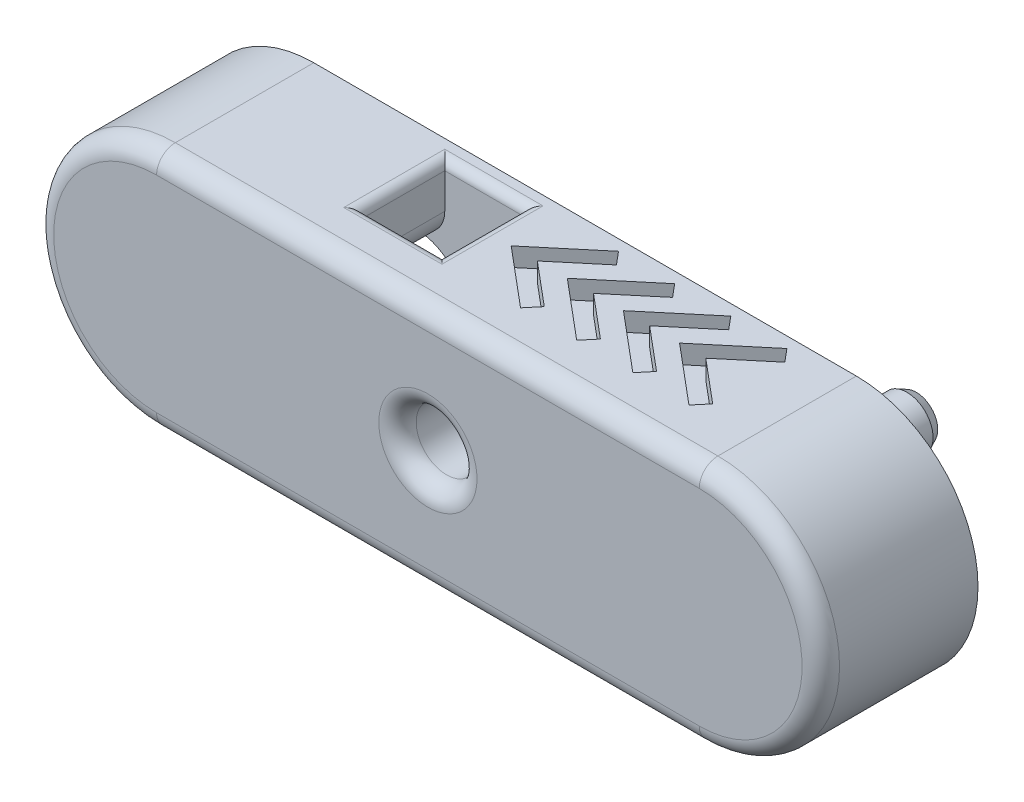
SolidWorks part; units mm, degrees
ref_plane "Front Plane" through (0, 0, 0) normal (0, 0, 1) x (1, 0, 0)
ref_plane "Top Plane" through (0, 0, 0) normal (0, 1, 0) x (1, 0, 0)
ref_plane "Right Plane" through (0, 0, 0) normal (1, 0, 0) x (0, 0, -1)
sketch "Sketch1" plane through (0, 0, 0) normal (0, 0, 1) x (1, 0, 0)
  line L0 (29, 13) -> (-29, 13) construction
  line L1 (-29, -13) -> (29, -13) construction
  line L2 (29, 13) -> (-29, 13)
  line L3 (-29, -13) -> (29, -13)
  arc A0 (-29, 13) -> (-29, -13) centre (-29, 0) ccw construction
  arc A1 (29, -13) -> (29, 13) centre (29, 0) ccw construction
  arc A2 (-29, 13) -> (-29, -13) centre (-29, 0) ccw
  arc A3 (29, -13) -> (29, 13) centre (29, 0) ccw
  circle A9 centre (-35, 0) radius 3 construction
  circle A10 centre (17, 6) radius 3 construction
  circle A11 centre (17, -6) radius 3 construction
  circle A12 centre (29, -6) radius 3 construction
  circle A13 centre (29, 6) radius 3 construction
  circle A14 centre (-35, 0) radius 3
  circle A15 centre (17, 6) radius 3
  circle A16 centre (17, -6) radius 3
  circle A17 centre (29, -6) radius 3
  circle A18 centre (29, 6) radius 3
  circle A19 centre (17, 6) radius 2.8
  circle A20 centre (29, 6) radius 2.8
  circle A21 centre (29, -6) radius 2.8
  circle A22 centre (17, -6) radius 2.8
  circle A23 centre (-35, 0) radius 2.8
  circle A24 centre (-16, 0) radius 5.05 construction
  circle A25 centre (0, 0) radius 5.05 construction
  circle A26 centre (-16, 0) radius 5.05
  circle A27 centre (0, 0) radius 5.05
  dimension "D1" = 0.2
extrude "Boss-Extrude1" add sketch "Sketch1" against normal offset from surface (6.4 mm away) 1 contours A23 | A20 | A21 region at (29, 6, 0) region at (29, -6, 0) region at (-35, 0, 0)
extrude "Boss-Extrude2" add sketch "Sketch1<3>" along normal blind 2 contours L3 A3 L2 A2 A27 A26 A18 A17 A16 A15 A14 | A14 | A16 | A17 | A18 | A15 region at (41.1207, 0, 0)
sketch "Sketch1<3>" plane through (0, 0, 0) normal (0, 0, 1) x (1, 0, 0) same geometry as "Sketch1"
sketch "Sketch5" plane through (0, 0, 2) normal (0, 0, 1) x (1, 0, 0)
  line L0 (-11.8, 13) -> (-11.8, -13) construction
  line L1 (29, 13) -> (-29, 13) construction
  line L2 (-29, -13) -> (29, -13) construction
  line L3 (-4.8, 13) -> (-4.8, -13) construction
  line L4 (-4.5, -13) -> (-4.5, -9.55)
  line L5 (-13, 13) -> (-29, 13)
  line L6 (-29, -13) -> (-13, -13)
  line L7 (0, -5.05) -> (0, 5.05) construction
  line L8 (29, -13) -> (-4.5, -13)
  line L9 (-4.5, 13) -> (29, 13)
  line L10 (-4.5, 13) -> (-4.5, 9.55)
  line L11 (-13, 13) -> (-13, 8.25)
  line L12 (-13, -13) -> (-13, -8.25)
  line L13 (-16, -5.25) -> (-16, 5.25) construction
  circle A2 centre (-16, 0) radius 5.05 construction
  circle A3 centre (-16, 0) radius 5.05
  circle A4 centre (-16, 0) radius 5.25
  arc A7 (-29, 13) -> (-29, -13) centre (-29, 0) ccw construction
  arc A8 (-29, 13) -> (-29, -13) centre (-29, 0) ccw
  circle A10 centre (0, 0) radius 5.05 construction
  circle A11 centre (0, 0) radius 5.05
  arc A14 (29, -13) -> (29, 13) centre (29, 0) ccw construction
  arc A15 (29, -13) -> (29, 13) centre (29, 0) ccw
  arc A18 (-4.5, -9.55) -> (0, -5.05) centre (0, -9.55) cw
  circle A20 centre (0, 0) radius 5.05 construction
  arc A21 (-4.5, 9.55) -> (0, 5.05) centre (0, 9.55) ccw
  arc A22 (-13, -8.25) -> (-16, -5.25) centre (-16, -8.25) ccw
  arc A23 (-13, 8.25) -> (-16, 5.25) centre (-16, 8.25) cw
  arc A25 (0, -5.05) -> (0, 5.05) centre (0, 0) ccw
  arc A26 (-16, 5.25) -> (-16, -5.25) centre (-16, 0) ccw
  circle M3 centre (0, 0) radius 5.05
  line M5 (-29, -13) -> (29, -13)
  arc M6 (29, -13) -> (29, 13) centre (29, 0) ccw
  line M7 (29, 13) -> (-29, 13)
  arc M8 (-29, 13) -> (-29, -13) centre (-29, 0) ccw
  dimension "D1" = 7
  dimension "D3" = 1.2
  dimension "D4" = 1.2
  dimension "D5" = 0.3
  dimension "D6" = 0.3
  dimension "D2" = 0.2
extrude "Boss-Extrude3" add sketch "Sketch5" along normal offset from surface (8.8 mm away) 0.8 contours M3 M5 M6 M7 | A4 M7 M8 M5 region at (19.0735, 0, 2) region at (-27.5385, 0, 2) offset beyond the face yes
sketch "Sketch6" plane through (0, 0, 10.8) normal (0, 0, 1) x (1, 0, 0)
  line L0 (29, 13) -> (-29, 13) construction
  line L1 (-29, -13) -> (29, -13) construction
  line L2 (29, 13) -> (-29, 13)
  line L3 (-29, -13) -> (29, -13)
  arc A0 (29, -13) -> (29, 13) centre (29, 0) ccw construction
  arc A1 (-29, 13) -> (-29, -13) centre (-29, 0) ccw construction
  arc A2 (29, -13) -> (29, 13) centre (29, 0) ccw
  arc A3 (-29, 13) -> (-29, -13) centre (-29, 0) ccw
  circle A4 centre (-16, 0) radius 5.05 construction
  circle A5 centre (-16, 0) radius 5.05
  circle A6 centre (0, 0) radius 3 construction
  circle A7 centre (0, 0) radius 3
  circle A8 centre (0, 0) radius 3.25
  arc M7 (-16, 5.25) -> (-13, 8.25) centre (-16, 8.25) ccw
  line M8 (-13, 8.25) -> (-13, 13)
  line M9 (-13, 13) -> (-29, 13)
  arc M10 (-29, 13) -> (-29, -13) centre (-29, 0) ccw
  line M11 (-29, -13) -> (-13, -13)
  line M12 (-13, -13) -> (-13, -8.25)
  arc M13 (-13, -8.25) -> (-16, -5.25) centre (-16, -8.25) ccw
  arc M14 (-16, -5.25) -> (-16, 5.25) centre (-16, 0) cw
  dimension "D1" = 0.25
extrude "Boss-Extrude4" add sketch "Sketch6" along normal blind 6 contours M14 M7 M8 M9 M10 M11 M12 M13 | L3 A2 L2 A8 A5 M8 M7 M14 M13 M12 | A5 region at (13.5183, 0, 10.8) region at (-27.5385, 0, 10.8) region at (-16, 0, 10.8)
extrude "Cut-Extrude1" cut sketch "Sketch6<4>" along normal offset from surface (4 mm away) 2 contours A5 up to face at (0, 0, 16.8)
sketch "Sketch6<4>" plane through (0, 0, 10.8) normal (0, 0, 1) x (1, 0, 0) same geometry as "Sketch6"
fillet "Fillet1" radius 2 5 edges at (3.25, 0, 16.8) (0, -13, 16.8) (-42, 0, 16.8) (0, 13, 16.8) (42, 0, 16.8)
fillet "Fillet2" radius 1 8 edges at (-8.75, 13, 2) (-13, 13, 6.4) (-8.75, 13, 10.8) (-4.5, 13, 6.4) (-13, -13, 6.4) (-8.75, -13, 2) (-4.5, -13, 6.4) (-8.75, -13, 10.8)
chamfer "Chamfer1" distance 0.5 distance2 1 3 edges at (26.2, -6, -6.4) (26.2, 6, -6.4) (-37.8, 0, -6.4) first distance on face at (26.2, -6, -6.4) first distance on face at (26.2, 6, -6.4) first distance on face at (-37.8, 0, -6.4)
sketch "Sketch7" plane through (0, 13, 0) normal (0, 1, 0) x (1, 0, 0)
  line L0 (-3.5, -6.4) -> (29, -6.4) construction
  line L2 (-3.5, -1) -> (-3.5, -11.8) construction
  line L6 (-1.5, -6.4) -> (4.7396, -11.6356)
  line L7 (4.7396, -11.6356) -> (5.8966, -10.2567)
  line L8 (5.8966, -10.2567) -> (1.3003, -6.4)
  line L9 (1.3003, -6.4) -> (5.8966, -2.5433)
  line L10 (5.8966, -2.5433) -> (4.7396, -1.1644)
  line L11 (4.7396, -1.1644) -> (-1.5, -6.4)
  line L12 (29, -14.8) -> (29, 0) construction
  line L13 (10.7396, -1.1644) -> (4.5, -6.4)
  line L14 (4.5, -6.4) -> (10.7396, -11.6356)
  line L15 (10.7396, -11.6356) -> (11.8966, -10.2567)
  line L16 (11.8966, -10.2567) -> (7.3003, -6.4)
  line L17 (7.3003, -6.4) -> (11.8966, -2.5433)
  line L18 (11.8966, -2.5433) -> (10.7396, -1.1644)
  line L19 (16.7396, -1.1644) -> (10.5, -6.4)
  line L20 (10.5, -6.4) -> (16.7396, -11.6356)
  line L21 (16.7396, -11.6356) -> (17.8966, -10.2567)
  line L22 (17.8966, -10.2567) -> (13.3003, -6.4)
  line L23 (13.3003, -6.4) -> (17.8966, -2.5433)
  line L24 (17.8966, -2.5433) -> (16.7396, -1.1644)
  line L25 (22.7396, -1.1644) -> (16.5, -6.4)
  line L26 (16.5, -6.4) -> (22.7396, -11.6356)
  line L27 (22.7396, -11.6356) -> (23.8966, -10.2567)
  line L28 (23.8966, -10.2567) -> (19.3003, -6.4)
  line L29 (19.3003, -6.4) -> (23.8966, -2.5433)
  line L30 (23.8966, -2.5433) -> (22.7396, -1.1644)
  dimension "D1" = 40
  dimension "D2" = 6
  dimension "D3" = 1.8
  dimension "D4" = 2
  dimension "D6" = 6
  dimension "D5" = 4
extrude "Cut-Extrude2" cut sketch "Sketch7" against normal blind 2
equation "\"D4@Sketch5\"=\"D3@Sketch5\""
equation "\"D5@Sketch5\"=\"D6@Sketch5\""
